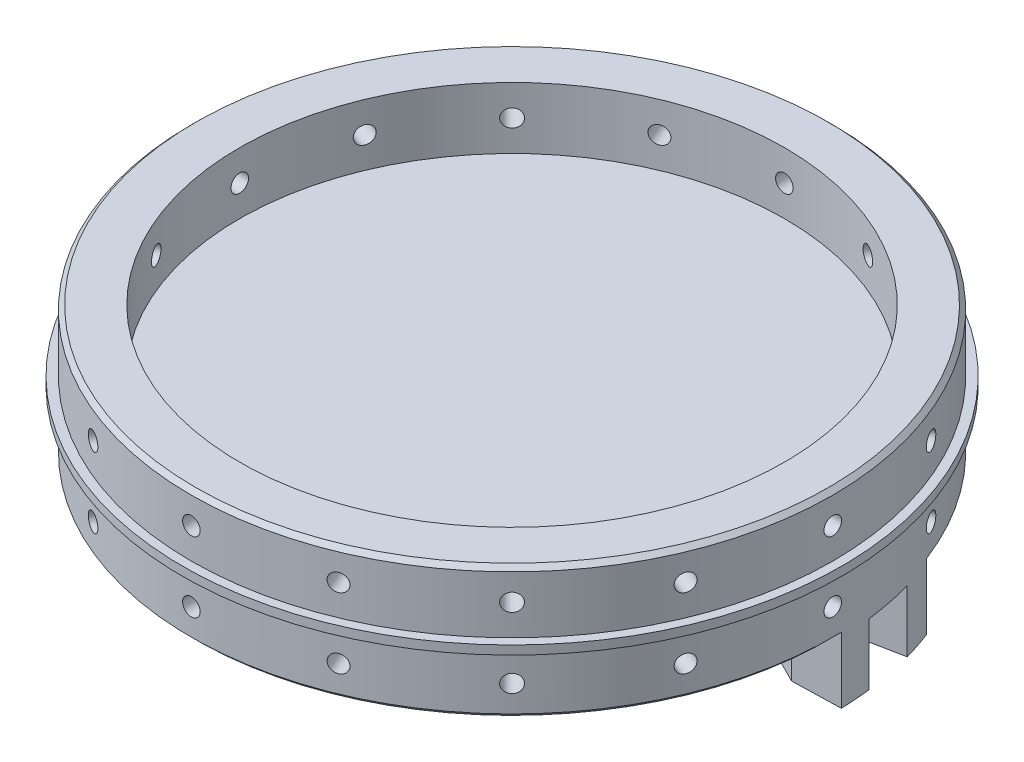
SolidWorks part; units mm, degrees
material "7075-T6, Plate (SS)"
ref_plane "Piano frontale" through (0, 0, 0) normal (0, 0, 1) x (1, 0, 0)
ref_plane "Piano superiore" through (0, 0, 0) normal (0, 1, 0) x (1, 0, 0)
ref_plane "Piano destro" through (0, 0, 0) normal (1, 0, 0) x (0, 0, -1)
sketch "Schizzo1" plane through (0, 0, 0) normal (0, 0, 1) x (1, 0, 0)
  line L1 (-73, 30) -> (-62, 30)
  line L5 (0, 0) -> (-73, 0) construction
  line L7 (-73, 14) -> (-73, 0)
  line L10 (0, 0) -> (0, 16) construction
  line L13 (-73, 14) -> (-75, 14)
  line L14 (-75, 14) -> (-75, 16)
  line L15 (-75, 16) -> (-73, 16)
  line L16 (-73, 16) -> (-73, 30)
  line L19 (-62, 16) -> (-62, 14) construction
  line L21 (-73, 14) -> (0, 14) construction
  line L22 (-73, 16) -> (0, 16) construction
  line L23 (0, 16) -> (0, 14) construction
  line L24 (-73, 0) -> (-62, 0)
  line L25 (-62, 30) -> (-62, 16)
  line L26 (-62, 0) -> (-62, 14)
  line L27 (-62, 16) -> (0, 16)
  line L28 (-62, 14) -> (0, 14)
  line L29 (0, 14) -> (0, 16)
  dimension "D1" = 146
  dimension "D2" = 2
  dimension "D3" = 150
  dimension "D4" = 11
  dimension "D5" = 62
  dimension "D6" = 14
  dimension "D7" = 14
revolve "Rivoluzione1" add sketch "Schizzo1" angle 360 about L10 region at (-57.6747, 15, 0)
hole_wizard "Ø4.0 (4) Diameter Hole1" positions "Schizzo3D1" profile "Schizzo5" hole size "Ø4.0" standard "ISO"
sketch3d "Schizzo3D1"
  line L0 (-73, 16, 0) -> (-73, 30, 0) construction
  circle A0 centre (0, 30, 0) radius 73 construction
  circle A1 centre (0, 30, 0) radius 73 construction
  circle A2 centre (0, 16, 0) radius 73 construction
  circle A3 centre (0, 16, 0) radius 73 construction
  point P0 (-73, 23, 0)
  point P4 (0, -43, 0)
  point P6 (0, -43, 0)
  point P9 (0, -57, 0)
  point P11 (0, -57, 0)
  point P17 (-73, 23, 0)
sketch "Schizzo5" plane through (-73, 23, 0) normal (0, 1, 0) x (0, 0, 1)
  line L0 (0, 0) -> (0, 19)
  line L1 (0, 19) -> (2, 17.7983)
  line L2 (2, 17.7983) -> (2, 0)
  line L5 (2, 0) -> (0, 0)
  line L10 (0, 19) -> (-2, 17.7983) construction
  line L11 (0, -6.35) -> (0, 107.95) construction
  dimension "Hole Dia." = 4
  dimension "Hole Depth" = 19
  dimension "Drill Angle" = 118
hole_wizard "Foro Ø4.0 (4)-3" positions "Schizzo3D3" profile "Schizzo9" hole size "Ø4.0" standard "ISO"
sketch3d "Schizzo3D3"
  line L0 (73, 0, 0) -> (73, 14, 0) construction
  circle A1 centre (0, 14, 0) radius 73 construction
  circle A3 centre (0, 14, 0) radius 73 construction
  circle A4 centre (0, 0, 0) radius 73 construction
  point P0 (73, 7, 0)
  point P2 (73, 7, 0)
  point P9 (0, -59, 0)
  point P13 (0, -59, 0)
  point P18 (73, 7, 0)
  point P22 (0, -73, 0)
sketch "Schizzo9" plane through (73, 7, 0) normal (0, 1, 0) x (0, 0, -1)
  line L0 (0, 0) -> (0, 19)
  line L1 (0, 19) -> (2, 17.7983)
  line L2 (2, 17.7983) -> (2, 0)
  line L5 (2, 0) -> (0, 0)
  line L10 (0, 19) -> (-2, 17.7983) construction
  line L11 (0, -6.35) -> (0, 107.95) construction
  dimension "Hole Dia." = 4
  dimension "Hole Depth" = 19
  dimension "Drill Angle" = 118
pattern_circular "RipetizioneCircolare7" count 16 over 360 about axis through (0, 14, 0) along (0, -1, 0) of "Foro Ø4.0 (4)-3"
pattern_circular "CirPattern1" count 16 over 360 about axis through (0, 16, 0) along (0, -1, 0) of "Ø4.0 (4) Diameter Hole1"
sketch "Schizzo2" plane through (0, 0, 0) normal (0, -1, 0) x (1, 0, 0)
  line L0 (-67.4432, 27.9359) -> (0, 0) construction
  line L4 (0, 0) -> (-73, 0) construction
  line L5 (0, 0) -> (-71.5973, 14.2416) construction
  line L6 (-67.4432, 27.9359) -> (-73, 0) construction
  line L7 (0, 0) -> (-68.169, 26.1148) construction
  line L8 (0, 0) -> (-72.9737, 1.9603) construction
  line L9 (-68.169, 26.1148) -> (-57.897, 22.1797)
  line L10 (-72.9737, 1.9603) -> (-61.9776, 1.6649)
  line L11 (0, 0) -> (-71.4656, 7.714) construction
  line L12 (0, 0) -> (-68.9776, 20.2219) construction
  line L13 (-71.4656, 7.714) -> (-71.5973, 14.2416) construction
  line L14 (-71.5973, 14.2416) -> (-68.9776, 20.2219) construction
  line L15 (-59.496, 17.4422) -> (-61.6419, 6.6536) construction
  line L16 (-61.9776, 1.6649) -> (-71.5973, 14.2416) construction
  line L17 (-57.897, 22.1797) -> (-71.5973, 14.2416) construction
  line L18 (-59.496, 17.4422) -> (-57.897, 22.1797) construction
  line L19 (-59.496, 17.4422) -> (-70.0517, 20.5368) construction
  line L20 (-61.6419, 6.6536) -> (-72.5784, 7.8341) construction
  line L21 (-53.6881, 5.7951) -> (-61.6419, 6.6536) construction
  line L22 (-51.8191, 15.1916) -> (-59.496, 17.4422) construction
  line L23 (-61.9776, 1.6649) -> (-53.6881, 5.7951)
  line L24 (-57.897, 22.1797) -> (-51.8191, 15.1916)
  line L25 (-61.6419, 6.6536) -> (-53.6881, 5.7951)
  line L26 (-59.496, 17.4422) -> (-51.8191, 15.1916)
  line L27 (-61.6419, 6.6536) -> (-72.4668, 8.8068)
  line L28 (-59.496, 17.4422) -> (-70.3208, 19.5954)
  line L29 (-72.4668, 8.8068) -> (-70.3208, 19.5954)
  arc A0 (-66.6525, 29.7732) -> (-68.1833, 26.0776) centre (0, 0) ccw construction
  arc A2 (-66.6525, 29.7732) -> (-68.1833, 26.0776) centre (0, 0) ccw construction
  arc A3 (-72.9726, 2) -> (-72.9726, -2) centre (0, 0) ccw construction
  arc A4 (-72.9726, 2) -> (-72.9726, -2) centre (0, 0) ccw construction
  arc A5 (-53.6881, 5.7951) -> (-51.8191, 15.1916) centre (0, 0) cw
  circle A7 centre (0, 0) radius 73 construction
  circle A8 centre (0, 0) radius 62 construction
  arc A9 (-68.169, 26.1148) -> (-72.9737, 1.9603) centre (0, 0) ccw
  arc A10 (-57.897, 22.1797) -> (-61.9776, 1.6649) centre (0, 0) ccw
  point P15 (-70.2216, 13.9679)
  circle M9 centre (0, 0) radius 62
  dimension "D3" = 11
  dimension "D1" = 8
  dimension "D4" = 5
extrude "Boss-Extrude16" add sketch "Schizzo2" against normal up to next contours L25 A5 L26 M9 region at (-56.9008, 0, 11.3183)
sketch "Sketch6" plane through (0, 0, 0) normal (0, -1, 0) x (1, 0, 0)
  line L0 (-61.6419, 6.6536) -> (-59.496, 17.4422)
  line L1 (-61.6419, 6.6536) -> (-72.4668, 8.8068)
  line L2 (-72.4668, 8.8068) -> (-70.3208, 19.5954) construction
  line L3 (-70.3208, 19.5954) -> (-59.496, 17.4422)
  line L4 (0, 0) -> (-68.169, 26.1148) construction
  line L5 (0, 0) -> (-72.9737, 1.9603) construction
  line L6 (-72.9737, 1.9603) -> (-61.6419, 6.6536) construction
  line L7 (-59.496, 17.4422) -> (-68.169, 26.1148) construction
  line L8 (-61.9776, 1.6649) -> (-53.6881, 5.7951)
  line L9 (-51.8191, 15.1916) -> (-57.897, 22.1797)
  line L10 (-72.9737, 1.9603) -> (-61.9776, 1.6649)
  line L11 (-68.169, 26.1148) -> (-57.897, 22.1797)
  line L12 (-61.9776, 1.6649) -> (-61.6419, 6.6536) construction
  circle A0 centre (0, 0) radius 73 construction
  arc A1 (-61.6419, 6.6536) -> (-59.496, 17.4422) centre (0, 0) ccw construction
  arc A2 (-61.6419, 6.6536) -> (-61.9776, 1.6649) centre (0, 0) ccw construction
  arc A4 (-68.169, 26.1148) -> (-72.9737, 1.9603) centre (0, 0) ccw
  arc A5 (-57.897, 22.1797) -> (-59.496, 17.4422) centre (0, 0) ccw construction
  arc A6 (-51.8191, 15.1916) -> (-53.6881, 5.7951) centre (0, 0) ccw construction
  arc A7 (-51.8191, 15.1916) -> (-53.6881, 5.7951) centre (0, 0) ccw
  point P0 (-59.496, 17.4422)
  point P1 (-61.6419, 6.6536)
  arc M8 (-59.496, 17.4422) -> (-61.6419, 6.6536) centre (0, 0) cw
  line M9 (-61.6419, 6.6536) -> (-53.6881, 5.7951)
  arc M10 (-53.6881, 5.7951) -> (-51.8191, 15.1916) centre (0, 0) cw
  line M11 (-51.8191, 15.1916) -> (-59.496, 17.4422)
  circle M12 centre (0, 0) radius 73
  dimension "D1" = 5
extrude "Boss-Extrude19" add sketch "Sketch6" along normal blind 14 contours L3 L1 L0 M12 | L10 L1 M12 M8 | L8 M8 M9 | L0 M9 M10 M11 | L9 M11 M8 | L11 L3 M12 M8 region at (-66.0494, 0, 13.138) region at (-67.5954, 0, 4.8067) region at (-59.1253, 0, 4.7) region at (-56.8171, 0, 11.3016) region at (-64.2895, 0, 21.4268) region at (-56.4233, 0, 18.2841)
sketch "Sketch3" plane through (0, -14, 0) normal (0, -1, 0) x (1, 0, 0)
  line L3 (-72.5784, 7.8341) -> (0, 0) construction
  line L4 (0, 0) -> (-70.0517, 20.5368) construction
  line L5 (-61.5444, 7.144) -> (-59.5935, 16.9518)
  line L8 (-62.1323, 6.7511) -> (-72.4668, 8.8068)
  line L9 (-72.4668, 8.8068) -> (-70.3208, 19.5954) construction
  line L10 (-70.3208, 19.5954) -> (-59.9863, 17.5398)
  line L11 (-61.5444, 7.144) -> (-62.1323, 6.7511)
  line L12 (-59.9863, 17.5398) -> (-59.5935, 16.9518)
  arc A0 (-68.169, 26.1148) -> (-72.9737, 1.9603) centre (0, 0) ccw construction
  arc A4 (-61.9776, 1.6649) -> (-57.897, 22.1797) centre (0, 0) cw construction
  arc A7 (-70.3208, 19.5954) -> (-72.4668, 8.8068) centre (0, 0) ccw
  point P11 (-61.6419, 6.6536)
  point P13 (-59.496, 17.4422)
extrude "Cut-Extrude3" cut sketch "Sketch3" against normal blind 14
chamfer "Chamfer1" distance 5 angle 45 2 edges at (-57.665, 0, 6.2243) (-55.6575, 0, 16.3169)
hole_wizard "Ø4.0 (4) Diameter Hole3" positions "3DSketch2" profile "Sketch4" hole size "Ø4.0" standard "ISO"
sketch3d "3DSketch2"
  line L2 (-61.5444, -14, 7.144) -> (-59.5935, -14, 16.9518) construction
  line L3 (-61.5444, -14, 7.144) -> (-59.5935, -14, 16.9518)
  line L4 (-61.5444, 0, 7.144) -> (-59.5935, 0, 16.9518) construction
  line L5 (-61.5444, 0, 7.144) -> (-59.5935, 0, 16.9518)
  line L6 (-60.569, -14, 12.0479) -> (-60.569, 0, 12.0479) construction
  point P32 (-60.569, -7, 12.0479)
  point P37 (-60.569, -7, 12.0479)
sketch "Sketch4" plane through (-60.569, -7, 12.0479) normal (0, 1, 0) x (0.1951, 0, 0.9808)
  line L0 (0, 0) -> (0, 19)
  line L1 (0, 19) -> (2, 17.7983)
  line L2 (2, 17.7983) -> (2, 0)
  line L5 (2, 0) -> (0, 0)
  line L10 (0, 19) -> (-2, 17.7983) construction
  line L11 (0, -6.35) -> (0, 107.95) construction
  dimension "Hole Dia." = 4
  dimension "Hole Depth" = 19
  dimension "Drill Angle" = 118
pattern_circular "CirPattern2" count 2 over 360 about axis through (0, 0, 0) along (0, -1, 0) of "Boss-Extrude16", "Boss-Extrude19", "Chamfer1", "Cut-Extrude3", "Ø4.0 (4) Diameter Hole3"
chamfer "Smusso3" distance 1 angle 45 1 edges at (0, 30, -73)
chamfer "Smusso1" distance 1 angle 45 2 edges at (14.2416, 0, 71.5973) (-14.2416, 0, -71.5973)
